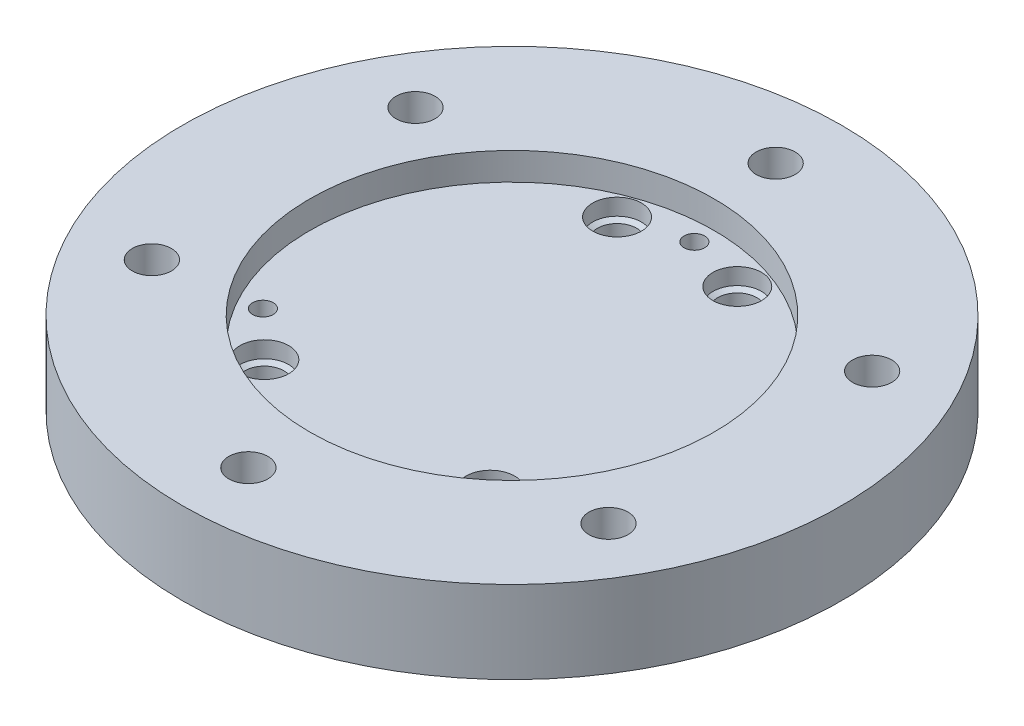
SolidWorks part; units mm, degrees
material "Copper"
ref_plane "Front Plane" through (0, 0, 0) normal (0, 0, 1) x (1, 0, 0)
ref_plane "Top Plane" through (0, 0, 0) normal (0, 1, 0) x (1, 0, 0)
ref_plane "Right Plane" through (0, 0, 0) normal (1, 0, 0) x (0, 0, -1)
ref_axis "Y Axis" through (0, 0.1588, 0) along (0, -1, 0)
sketch "outer" plane through (0, 0, 0) normal (0, 1, 0) x (1, 0, 0)
  circle A0 centre (0, 0) radius 19.05
  dimension "D1" = 38.1
extrude "Body" add sketch "outer" against normal blind 4.7625
sketch "inner" plane through (0, 0, 0) normal (0, 1, 0) x (1, 0, 0)
  circle A0 centre (0, 0) radius 11.684
  dimension "D1" = 23.368
extrude "Pocket" cut sketch "inner" against normal blind 1.5875
sketch "Screw Position" plane through (0, 0, 0) normal (0, 1, 0) x (1, 0, 0)
  point P0 (0, -15.24)
  dimension "D1" = 15.24
hole_wizard "#4-40 Tapped Hole3" positions "Sketch12" profile "Sketch13" tap size "#4-40" standard "ANSI Inch" end condition through all
sketch "Sketch12" plane through (0, 0, 0) normal (0, 1, 0) x (1, 0, 0)
  point P0 (0, -15.24)
sketch "Sketch13" plane through (0, 0, 15.24) normal (1, 0, 0) x (0, 0, 1)
  line L0 (0, 0) -> (0, 4.7625)
  line L1 (0, 4.7625) -> (1.1303, 4.7625)
  line L2 (1.1303, 4.7625) -> (1.1303, 0)
  line L5 (1.1303, 0) -> (0, 0)
  line L11 (0, -6.35) -> (0, 107.95) construction
  dimension "Thru Tap Drill Dia." = 2.2606
  dimension "Thru Tap Drill Depth" = 4.7625
cosmetic thread "Hole Thread3" parameters "D2"=2.8448
pattern_circular "Screw Holes" count 6 over 360 about axis through (0, 0.1588, 0) along (0, -1, 0) of "#4-40 Tapped Hole3"
sketch "Inner Screw Position" plane through (0, 0, 0) normal (0, 1, 0) x (1, 0, 0)
  point P0 (0, 10.541)
  dimension "D1" = 10.541
hole_wizard "#0-80 Tapped Hole1" positions "Sketch16" profile "Sketch17" tap size "#0-80" standard "ANSI Inch" end condition through all
sketch "Sketch16" plane through (0, -1.5875, 0) normal (0, 1, 0) x (1, 0, 0)
  point P0 (0, 10.541)
sketch "Sketch17" plane through (0, -1.5875, -10.541) normal (1, 0, 0) x (0, 0, 1)
  line L0 (0, 0) -> (0, 3.175)
  line L1 (0, 3.175) -> (0.5956, 3.175)
  line L2 (0.5956, 3.175) -> (0.5956, 0)
  line L5 (0.5956, 0) -> (0, 0)
  line L11 (0, -6.35) -> (0, 107.95) construction
  dimension "Thru Tap Drill Dia." = 1.1913
  dimension "Thru Tap Drill Depth" = 3.175
cosmetic thread "Hole Thread4" parameters "D2"=1.524
pattern_circular "Inner Screw Holes" count 3 over 360 about axis through (0, 0.1588, 0) along (0, -1, 0) of "#0-80 Tapped Hole1"
sketch "IO Postions" plane through (0, 0, 0) normal (0, 1, 0) x (1, 0, 0)
  line L0 (0, 0) -> (-3.4749, 9.5473) construction
  line L1 (0, 0) -> (-5.9719, 8.2196) construction
  point P0 (-3.4749, 9.5473)
  point P5 (-5.9719, 8.2196)
  point P6 (-8.0062, 6.2551)
  point P7 (-9.4202, 3.806)
  point P8 (-10.1043, 1.062)
  point P9 (-10.0056, -1.7643)
  point P13 (10.0056, -1.7643)
  point P14 (10.1043, 1.062)
  point P15 (9.4202, 3.806)
  point P16 (8.0062, 6.2551)
  point P17 (5.9719, 8.2196)
  point P18 (3.4749, 9.5473)
  point P19 (-6.5307, -7.783)
  point P20 (-4.1324, -9.2816)
  point P21 (-1.414, -10.0611)
  point P22 (1.414, -10.0611)
  point P23 (4.1324, -9.2816)
  point P24 (6.5307, -7.783)
  point P25 (0, 0)
  dimension "D3" = 16
  dimension "D2" = 6
  dimension "D4" = 3
hole_wizard "#43 (0.089) Diameter Hole1" positions "Sketch20" profile "Sketch21" hole size "#43" standard "ANSI Inch" end condition through all
sketch "Sketch20" plane through (0, -1.5875, 0) normal (0, 1, 0) x (1, 0, 0)
  point P0 (-3.4749, 9.5473)
sketch "Sketch21" plane through (-3.4749, -1.5875, -9.5473) normal (1, 0, 0) x (0, 0, 1)
  line L0 (0, 0) -> (0, 3.175)
  line L1 (0, 3.175) -> (1.1303, 3.175)
  line L2 (1.1303, 3.175) -> (1.1303, 0)
  line L5 (1.1303, 0) -> (0, 0)
  line L11 (0, -6.35) -> (0, 107.95) construction
  dimension "Thru Hole Dia." = 2.2606
  dimension "Thru Hole Depth" = 3.175
hole_wizard "#34 (0.111) Diameter Hole1" positions "Sketch22" profile "Sketch23" hole size "#34" standard "ANSI Inch"
sketch "Sketch22" plane through (0, -1.5875, 0) normal (0, 1, 0) x (1, 0, 0)
  point P0 (-3.4749, 9.5473)
sketch "Sketch23" plane through (-3.4749, -1.5875, -9.5473) normal (1, 0, 0) x (0, 0, 1)
  line L0 (0, 0) -> (0, 1.7995)
  line L1 (0, 1.7995) -> (1.4097, 0.9525)
  line L2 (1.4097, 0.9525) -> (1.4097, 0)
  line L5 (1.4097, 0) -> (0, 0)
  line L10 (0, 1.7995) -> (-1.4097, 0.9525) construction
  line L11 (0, -6.35) -> (0, 107.95) construction
  dimension "Hole Dia." = 2.8194
  dimension "Hole Depth" = 0.9525
  dimension "Drill Angle" = 118
hole_wizard "#34 (0.111) Diameter Hole2" positions "Sketch28" profile "Sketch27" hole size "#34" standard "ANSI Inch"
sketch "Sketch28" plane through (0, -4.7625, 0) normal (0, -1, 0) x (-1, 0, 0)
  point P0 (3.4749, 9.5473)
sketch "Sketch27" plane through (-3.4749, -4.7625, -9.5473) normal (1, 0, 0) x (0, 0, -1)
  line L0 (0, 0) -> (0, 1.7995)
  line L1 (0, 1.7995) -> (1.4097, 0.9525)
  line L2 (1.4097, 0.9525) -> (1.4097, 0)
  line L5 (1.4097, 0) -> (0, 0)
  line L10 (0, 1.7995) -> (-1.4097, 0.9525) construction
  line L11 (0, -6.35) -> (0, 107.95) construction
  dimension "Hole Dia." = 2.8194
  dimension "Hole Depth" = 0.9525
  dimension "Drill Angle" = 118
sketch "IO Hole Position" plane through (0, 0, 0) normal (0, 1, 0) x (1, 0, 0)
  point P0 (3.4749, 9.5473)
  point P1 (-6.5307, -7.783)
  point P3 (6.5307, -7.783)
pattern_sketch "IO Holes Pattern" of "#43 (0.089) Diameter Hole1", "#34 (0.111) Diameter Hole1", "#34 (0.111) Diameter Hole2" driven by "IO Hole Position"
equation "\"outer_d\"= 3 / 2in"
equation "\"screw_r\"= 0.6in"
equation "\"inner_d\"= 0.920in"
equation "\"bottom_h\"= 3 / 16in"
equation "\"pocket_h\"= 1 / 16in"
equation "\"screw_inner_r\"= 0.415in"
equation "\"io_r\"= 0.4in"
equation "\"D1@outer\" = \"outer_d\""
equation "\"D1@Body\" = \"bottom_h\""
equation "\"D1@inner\" = \"inner_d\""
equation "\"D1@Pocket\"=\"pocket_h\""
equation "\"D1@Screw Position\" = \"screw_r\""
equation "\"D1@Inner Screw Position\" = \"screw_inner_r\""
equation "\"D1@IO Postions\" = \"io_r\""
